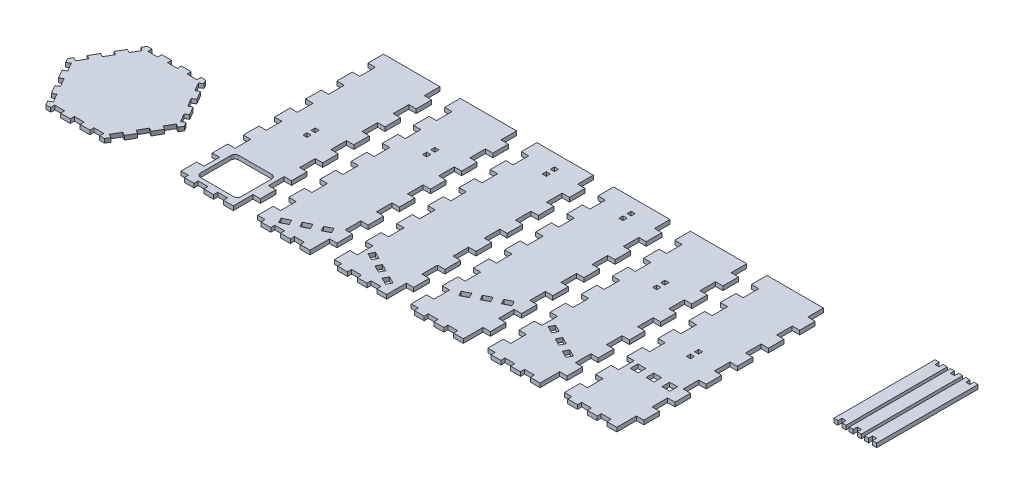
SolidWorks part; units mm, degrees
ref_plane "Front Plane" through (0, 0, 0) normal (0, 0, 1) x (1, 0, 0)
ref_plane "Top Plane" through (0, 0, 0) normal (0, 1, 0) x (1, 0, 0)
ref_plane "Right Plane" through (0, 0, 0) normal (1, 0, 0) x (0, 0, -1)
sketch "Sketch1" plane through (0, 0, 0) normal (0, 1, 0) x (1, 0, 0)
  line L0 (-22.87, -39.612) -> (-19.175, -39.612)
  line L13 (-19.175, -39.612) -> (-19.175, -36.412)
  line L14 (-19.175, -36.412) -> (-11.505, -36.412)
  line L15 (-11.505, -36.412) -> (-11.505, -39.612)
  line L16 (-11.505, -39.612) -> (-3.835, -39.612)
  line L17 (-3.835, -39.612) -> (-3.835, -36.412)
  line L18 (-3.835, -36.412) -> (3.835, -36.412)
  line L19 (3.835, -36.412) -> (3.835, -39.612)
  line L21 (-45.74, 0) -> (-43.8925, -3.2)
  line L22 (3.835, -39.612) -> (11.505, -39.612)
  line L23 (11.505, -39.612) -> (11.505, -36.412)
  line L24 (11.505, -36.412) -> (19.175, -36.412)
  line L25 (19.175, -36.412) -> (19.175, -39.612)
  line L26 (19.175, -39.612) -> (22.87, -39.612)
  line L27 (22.87, -39.612) -> (24.7175, -36.412)
  line L28 (45.74, 0) -> (22.87, 39.612) construction
  line L29 (24.7175, -36.412) -> (21.9462, -34.812)
  line L30 (21.9462, -34.812) -> (25.7812, -28.1696)
  line L31 (25.7812, -28.1696) -> (28.5525, -29.7696)
  line L32 (28.5525, -29.7696) -> (32.3875, -23.1272)
  line L33 (32.3875, -23.1272) -> (29.6162, -21.5272)
  line L34 (29.6162, -21.5272) -> (33.4512, -14.8848)
  line L35 (33.4512, -14.8848) -> (36.2225, -16.4848)
  line L36 (36.2225, -16.4848) -> (40.0575, -9.8424)
  line L37 (40.0575, -9.8424) -> (37.2862, -8.2424)
  line L38 (37.2862, -8.2424) -> (41.1212, -1.6)
  line L39 (41.1212, -1.6) -> (43.8925, -3.2)
  line L40 (43.8925, -3.2) -> (45.74, 0)
  line L41 (45.74, 0) -> (43.8925, 3.2)
  line L42 (22.87, 39.612) -> (-22.87, 39.612) construction
  line L43 (-22.87, 39.612) -> (-45.74, 0) construction
  line L44 (43.8925, 3.2) -> (41.1212, 1.6)
  line L45 (41.1212, 1.6) -> (37.2862, 8.2424)
  line L46 (37.2862, 8.2424) -> (40.0575, 9.8424)
  line L47 (40.0575, 9.8424) -> (36.2225, 16.4848)
  line L48 (36.2225, 16.4848) -> (33.4512, 14.8848)
  line L49 (33.4512, 14.8848) -> (29.6162, 21.5272)
  line L50 (29.6162, 21.5272) -> (32.3875, 23.1272)
  line L51 (32.3875, 23.1272) -> (28.5525, 29.7696)
  line L52 (28.5525, 29.7696) -> (25.7812, 28.1696)
  line L53 (25.7812, 28.1696) -> (21.9462, 34.812)
  line L54 (21.9462, 34.812) -> (24.7175, 36.412)
  line L55 (24.7175, 36.412) -> (22.87, 39.612)
  line L56 (22.87, 39.612) -> (19.175, 39.612)
  line L57 (-45.74, 0) -> (-22.87, -39.612) construction
  line L58 (-22.87, -39.612) -> (22.87, -39.612) construction
  line L59 (19.175, 39.612) -> (19.175, 36.412)
  line L60 (19.175, 36.412) -> (11.505, 36.412)
  line L61 (11.505, 36.412) -> (11.505, 39.612)
  line L62 (11.505, 39.612) -> (3.835, 39.612)
  line L63 (3.835, 39.612) -> (3.835, 36.412)
  line L64 (3.835, 36.412) -> (-3.835, 36.412)
  line L65 (-3.835, 36.412) -> (-3.835, 39.612)
  line L66 (-3.835, 39.612) -> (-11.505, 39.612)
  line L67 (-11.505, 39.612) -> (-11.505, 36.412)
  line L68 (-11.505, 36.412) -> (-19.175, 36.412)
  line L69 (-19.175, 36.412) -> (-19.175, 39.612)
  line L70 (-19.175, 39.612) -> (-22.87, 39.612)
  line L71 (-22.87, 39.612) -> (-24.7175, 36.412)
  line L72 (22.87, -39.612) -> (45.74, 0) construction
  line L73 (-43.8925, -3.2) -> (-41.1212, -1.6)
  line L74 (-24.7175, 36.412) -> (-21.9462, 34.812)
  line L75 (-21.9462, 34.812) -> (-25.7812, 28.1696)
  line L76 (-25.7812, 28.1696) -> (-28.5525, 29.7696)
  line L77 (-28.5525, 29.7696) -> (-32.3875, 23.1272)
  line L78 (-32.3875, 23.1272) -> (-29.6162, 21.5272)
  line L79 (-29.6162, 21.5272) -> (-33.4512, 14.8848)
  line L80 (-33.4512, 14.8848) -> (-36.2225, 16.4848)
  line L81 (-36.2225, 16.4848) -> (-40.0575, 9.8424)
  line L82 (-40.0575, 9.8424) -> (-37.2862, 8.2424)
  line L83 (-37.2862, 8.2424) -> (-41.1212, 1.6)
  line L84 (-41.1212, 1.6) -> (-43.8925, 3.2)
  line L85 (-43.8925, 3.2) -> (-45.74, 0)
  line L86 (-41.1212, -1.6) -> (-37.2862, -8.2424)
  line L87 (-37.2862, -8.2424) -> (-40.0575, -9.8424)
  line L88 (-40.0575, -9.8424) -> (-36.2225, -16.4848)
  line L89 (-36.2225, -16.4848) -> (-33.4512, -14.8848)
  line L90 (-33.4512, -14.8848) -> (-29.6162, -21.5272)
  line L91 (-29.6162, -21.5272) -> (-32.3875, -23.1272)
  line L92 (-32.3875, -23.1272) -> (-28.5525, -29.7696)
  line L93 (-28.5525, -29.7696) -> (-25.7812, -28.1696)
  line L94 (-25.7812, -28.1696) -> (-21.9462, -34.812)
  line L95 (-21.9462, -34.812) -> (-24.7175, -36.412)
  line L96 (-24.7175, -36.412) -> (-22.87, -39.612)
  line L97 (-21.9462, -34.812) -> (-19.175, -39.612) construction
  line L102 (19.175, -36.412) -> (24.7175, -36.412) construction
  line L103 (-19.175, -36.412) -> (-24.7175, -36.412) construction
  line L104 (80.5528, -34.8794) -> (88.2227, -34.8794)
  line L105 (88.2227, -34.8794) -> (88.2227, -31.6794)
  line L106 (88.2227, -31.6794) -> (95.8927, -31.6794)
  line L107 (95.8927, -31.6794) -> (95.8927, -34.8794)
  line L108 (95.8927, -34.8794) -> (103.5627, -34.8794)
  line L109 (103.5627, -34.8794) -> (103.5627, -31.6794)
  line L110 (103.5627, -31.6794) -> (111.2327, -31.6794)
  line L111 (111.2327, -31.6794) -> (111.2327, -34.8794)
  line L112 (111.2327, -34.8794) -> (118.9027, -34.8794)
  line L113 (80.5528, -34.8794) -> (80.5528, -31.6794)
  line L114 (80.5528, -31.6794) -> (74.8102, -31.6794)
  line L115 (74.8102, -31.6794) -> (74.8102, -19.4911)
  line L116 (74.8102, -19.4911) -> (80.5528, -19.4911)
  line L117 (80.5528, -19.4911) -> (80.5528, -7.3028)
  line L118 (80.5528, -7.3028) -> (74.8102, -7.3028)
  line L121 (118.9027, -7.3028) -> (124.6452, -7.3028)
  line L122 (124.6452, -7.3028) -> (124.6452, -19.4911)
  line L123 (124.6452, -19.4911) -> (118.9027, -19.4911)
  line L124 (118.9027, -19.4911) -> (118.9027, -34.8794)
  line L126 (21.9462, -34.812) -> (19.175, -39.612) construction
  line L250 (140.5528, -34.8794) -> (148.2227, -34.8794)
  line L265 (148.2227, -34.8794) -> (148.2227, -31.6794)
  line L266 (148.2227, -31.6794) -> (155.8927, -31.6794)
  line L267 (155.8927, -31.6794) -> (155.8927, -34.8794)
  line L268 (155.8927, -34.8794) -> (163.5627, -34.8794)
  line L269 (163.5627, -34.8794) -> (163.5627, -31.6794)
  line L270 (74.8102, -7.3028) -> (74.8102, 4.8855)
  line L271 (74.8102, 4.8855) -> (80.5528, 4.8855)
  line L272 (80.5528, 4.8855) -> (80.5528, 17.0739)
  line L273 (80.5528, 17.0739) -> (74.8102, 17.0739)
  line L274 (74.8102, 17.0739) -> (74.8102, 29.2622)
  line L275 (74.8102, 29.2622) -> (80.5528, 29.2622)
  line L276 (80.5528, 29.2622) -> (80.5528, 41.4505)
  line L277 (80.5528, 41.4505) -> (74.8102, 41.4505)
  line L278 (74.8102, 41.4505) -> (74.8102, 53.6388)
  line L279 (74.8102, 53.6388) -> (80.5528, 53.6388)
  line L280 (80.5528, 53.6388) -> (80.5528, 65.8271)
  line L281 (80.5528, 65.8271) -> (74.8102, 65.8271)
  line L282 (74.8102, 65.8271) -> (74.8102, 78.0154)
  line L283 (74.8102, 78.0154) -> (80.5528, 78.0154)
  line L284 (80.5528, 78.0154) -> (80.5528, 90.2037)
  line L285 (80.5528, 90.2037) -> (74.8102, 90.2037)
  line L286 (74.8102, 90.2037) -> (74.8102, 102.392)
  line L287 (74.8102, 102.392) -> (80.5528, 102.392)
  line L288 (80.5528, 102.392) -> (80.5528, 114.5803)
  line L289 (80.5528, 114.5803) -> (74.8102, 114.5803)
  line L290 (74.8102, 114.5803) -> (74.8102, 126.7686)
  line L291 (118.9027, -7.3028) -> (118.9027, 4.8855)
  line L292 (118.9027, 4.8855) -> (124.6452, 4.8855)
  line L293 (124.6452, 4.8855) -> (124.6452, 17.0739)
  line L294 (124.6452, 17.0739) -> (118.9027, 17.0739)
  line L295 (118.9027, 17.0739) -> (118.9027, 29.2622)
  line L296 (118.9027, 29.2622) -> (124.6452, 29.2622)
  line L297 (124.6452, 29.2622) -> (124.6452, 41.4505)
  line L298 (124.6452, 41.4505) -> (118.9027, 41.4505)
  line L299 (118.9027, 41.4505) -> (118.9027, 53.6388)
  line L300 (118.9027, 53.6388) -> (124.6452, 53.6388)
  line L301 (124.6452, 53.6388) -> (124.6452, 65.8271)
  line L302 (124.6452, 65.8271) -> (118.9027, 65.8271)
  line L303 (118.9027, 65.8271) -> (118.9027, 78.0154)
  line L304 (118.9027, 78.0154) -> (124.6452, 78.0154)
  line L305 (124.6452, 78.0154) -> (124.6452, 90.2037)
  line L306 (124.6452, 90.2037) -> (118.9027, 90.2037)
  line L307 (118.9027, 90.2037) -> (118.9027, 102.392)
  line L308 (118.9027, 102.392) -> (124.6452, 102.392)
  line L309 (124.6452, 102.392) -> (124.6452, 114.5803)
  line L310 (124.6452, 114.5803) -> (118.9027, 114.5803)
  line L311 (118.9027, 114.5803) -> (118.9027, 126.7686)
  line L312 (163.5627, -31.6794) -> (171.2327, -31.6794)
  line L313 (171.2327, -31.6794) -> (171.2327, -34.8794)
  line L314 (171.2327, -34.8794) -> (178.9027, -34.8794)
  line L315 (140.5528, -34.8794) -> (140.5528, -31.6794)
  line L316 (140.5528, -31.6794) -> (134.8102, -31.6794)
  line L317 (134.8102, -31.6794) -> (134.8102, -19.4911)
  line L318 (134.8102, -19.4911) -> (140.5528, -19.4911)
  line L319 (140.5528, -19.4911) -> (140.5528, -7.3028)
  line L320 (140.5528, -7.3028) -> (134.8102, -7.3028)
  line L322 (178.9027, -7.3028) -> (184.6452, -7.3028)
  line L323 (184.6452, -7.3028) -> (184.6452, -19.4911)
  line L324 (184.6452, -19.4911) -> (178.9027, -19.4911)
  line L325 (178.9027, -19.4911) -> (178.9027, -34.8794)
  line L326 (134.8102, -7.3028) -> (134.8102, 4.8855)
  line L327 (134.8102, 4.8855) -> (140.5528, 4.8855)
  line L328 (140.5528, 4.8855) -> (140.5528, 17.0739)
  line L329 (140.5528, 17.0739) -> (134.8102, 17.0739)
  line L330 (134.8102, 17.0739) -> (134.8102, 29.2622)
  line L331 (134.8102, 29.2622) -> (140.5528, 29.2622)
  line L332 (140.5528, 29.2622) -> (140.5528, 41.4505)
  line L333 (140.5528, 41.4505) -> (134.8102, 41.4505)
  line L334 (134.8102, 41.4505) -> (134.8102, 53.6388)
  line L335 (134.8102, 53.6388) -> (140.5528, 53.6388)
  line L336 (140.5528, 53.6388) -> (140.5528, 65.8271)
  line L337 (140.5528, 65.8271) -> (134.8102, 65.8271)
  line L338 (134.8102, 65.8271) -> (134.8102, 78.0154)
  line L339 (134.8102, 78.0154) -> (140.5528, 78.0154)
  line L340 (140.5528, 78.0154) -> (140.5528, 90.2037)
  line L341 (140.5528, 90.2037) -> (134.8102, 90.2037)
  line L342 (134.8102, 90.2037) -> (134.8102, 102.392)
  line L343 (134.8102, 102.392) -> (140.5528, 102.392)
  line L344 (140.5528, 102.392) -> (140.5528, 114.5803)
  line L345 (140.5528, 114.5803) -> (134.8102, 114.5803)
  line L346 (134.8102, 114.5803) -> (134.8102, 126.7686)
  line L347 (178.9027, -7.3028) -> (178.9027, 4.8855)
  line L348 (178.9027, 4.8855) -> (184.6452, 4.8855)
  line L349 (184.6452, 4.8855) -> (184.6452, 17.0739)
  line L350 (184.6452, 17.0739) -> (178.9027, 17.0739)
  line L351 (178.9027, 17.0739) -> (178.9027, 29.2622)
  line L352 (178.9027, 29.2622) -> (184.6452, 29.2622)
  line L353 (184.6452, 29.2622) -> (184.6452, 41.4505)
  line L354 (184.6452, 41.4505) -> (178.9027, 41.4505)
  line L355 (178.9027, 41.4505) -> (178.9027, 53.6388)
  line L356 (178.9027, 53.6388) -> (184.6452, 53.6388)
  line L357 (184.6452, 53.6388) -> (184.6452, 65.8271)
  line L358 (184.6452, 65.8271) -> (178.9027, 65.8271)
  line L359 (178.9027, 65.8271) -> (178.9027, 78.0154)
  line L360 (178.9027, 78.0154) -> (184.6452, 78.0154)
  line L361 (184.6452, 78.0154) -> (184.6452, 90.2037)
  line L362 (184.6452, 90.2037) -> (178.9027, 90.2037)
  line L363 (178.9027, 90.2037) -> (178.9027, 102.392)
  line L364 (178.9027, 102.392) -> (184.6452, 102.392)
  line L365 (184.6452, 102.392) -> (184.6452, 114.5803)
  line L366 (184.6452, 114.5803) -> (178.9027, 114.5803)
  line L367 (178.9027, 114.5803) -> (178.9027, 126.7686)
  line L369 (200.5528, -34.8794) -> (208.2227, -34.8794)
  line L370 (208.2227, -34.8794) -> (208.2227, -31.6794)
  line L371 (208.2227, -31.6794) -> (215.8927, -31.6794)
  line L372 (215.8927, -31.6794) -> (215.8927, -34.8794)
  line L373 (215.8927, -34.8794) -> (223.5627, -34.8794)
  line L374 (223.5627, -34.8794) -> (223.5627, -31.6794)
  line L375 (223.5627, -31.6794) -> (231.2327, -31.6794)
  line L376 (231.2327, -31.6794) -> (231.2327, -34.8794)
  line L377 (231.2327, -34.8794) -> (238.9027, -34.8794)
  line L378 (200.5528, -34.8794) -> (200.5528, -31.6794)
  line L379 (200.5528, -31.6794) -> (194.8102, -31.6794)
  line L380 (194.8102, -31.6794) -> (194.8102, -19.4911)
  line L381 (194.8102, -19.4911) -> (200.5528, -19.4911)
  line L382 (200.5528, -19.4911) -> (200.5528, -7.3028)
  line L383 (200.5528, -7.3028) -> (194.8102, -7.3028)
  line L385 (238.9027, -7.3028) -> (244.6452, -7.3028)
  line L386 (244.6452, -7.3028) -> (244.6452, -19.4911)
  line L387 (244.6452, -19.4911) -> (238.9027, -19.4911)
  line L388 (238.9027, -19.4911) -> (238.9027, -34.8794)
  line L389 (194.8102, -7.3028) -> (194.8102, 4.8855)
  line L390 (194.8102, 4.8855) -> (200.5528, 4.8855)
  line L391 (200.5528, 4.8855) -> (200.5528, 17.0739)
  line L392 (200.5528, 17.0739) -> (194.8102, 17.0739)
  line L393 (194.8102, 17.0739) -> (194.8102, 29.2622)
  line L394 (194.8102, 29.2622) -> (200.5528, 29.2622)
  line L395 (200.5528, 29.2622) -> (200.5528, 41.4505)
  line L396 (200.5528, 41.4505) -> (194.8102, 41.4505)
  line L397 (194.8102, 41.4505) -> (194.8102, 53.6388)
  line L398 (194.8102, 53.6388) -> (200.5528, 53.6388)
  line L399 (200.5528, 53.6388) -> (200.5528, 65.8271)
  line L400 (200.5528, 65.8271) -> (194.8102, 65.8271)
  line L401 (194.8102, 65.8271) -> (194.8102, 78.0154)
  line L402 (194.8102, 78.0154) -> (200.5528, 78.0154)
  line L403 (200.5528, 78.0154) -> (200.5528, 90.2037)
  line L404 (200.5528, 90.2037) -> (194.8102, 90.2037)
  line L405 (194.8102, 90.2037) -> (194.8102, 102.392)
  line L406 (194.8102, 102.392) -> (200.5528, 102.392)
  line L407 (200.5528, 102.392) -> (200.5528, 114.5803)
  line L408 (200.5528, 114.5803) -> (194.8102, 114.5803)
  line L409 (194.8102, 114.5803) -> (194.8102, 126.7686)
  line L410 (238.9027, -7.3028) -> (238.9027, 4.8855)
  line L411 (238.9027, 4.8855) -> (244.6452, 4.8855)
  line L412 (244.6452, 4.8855) -> (244.6452, 17.0739)
  line L413 (244.6452, 17.0739) -> (238.9027, 17.0739)
  line L414 (238.9027, 17.0739) -> (238.9027, 29.2622)
  line L415 (238.9027, 29.2622) -> (244.6452, 29.2622)
  line L416 (244.6452, 29.2622) -> (244.6452, 41.4505)
  line L417 (244.6452, 41.4505) -> (238.9027, 41.4505)
  line L418 (238.9027, 41.4505) -> (238.9027, 53.6388)
  line L419 (238.9027, 53.6388) -> (244.6452, 53.6388)
  line L420 (244.6452, 53.6388) -> (244.6452, 65.8271)
  line L421 (244.6452, 65.8271) -> (238.9027, 65.8271)
  line L422 (238.9027, 65.8271) -> (238.9027, 78.0154)
  line L423 (238.9027, 78.0154) -> (244.6452, 78.0154)
  line L424 (244.6452, 78.0154) -> (244.6452, 90.2037)
  line L425 (244.6452, 90.2037) -> (238.9027, 90.2037)
  line L426 (238.9027, 90.2037) -> (238.9027, 102.392)
  line L427 (238.9027, 102.392) -> (244.6452, 102.392)
  line L428 (244.6452, 102.392) -> (244.6452, 114.5803)
  line L429 (244.6452, 114.5803) -> (238.9027, 114.5803)
  line L430 (238.9027, 114.5803) -> (238.9027, 126.7686)
  line L432 (260.5528, -34.8794) -> (268.2227, -34.8794)
  line L433 (268.2227, -34.8794) -> (268.2227, -31.6794)
  line L434 (268.2227, -31.6794) -> (275.8927, -31.6794)
  line L435 (275.8927, -31.6794) -> (275.8927, -34.8794)
  line L436 (275.8927, -34.8794) -> (283.5627, -34.8794)
  line L437 (283.5627, -34.8794) -> (283.5627, -31.6794)
  line L438 (283.5627, -31.6794) -> (291.2327, -31.6794)
  line L439 (291.2327, -31.6794) -> (291.2327, -34.8794)
  line L440 (291.2327, -34.8794) -> (298.9027, -34.8794)
  line L441 (260.5528, -34.8794) -> (260.5528, -31.6794)
  line L442 (260.5528, -31.6794) -> (254.8102, -31.6794)
  line L443 (254.8102, -31.6794) -> (254.8102, -19.4911)
  line L444 (254.8102, -19.4911) -> (260.5528, -19.4911)
  line L445 (260.5528, -19.4911) -> (260.5528, -7.3028)
  line L446 (260.5528, -7.3028) -> (254.8102, -7.3028)
  line L448 (298.9027, -7.3028) -> (304.6452, -7.3028)
  line L449 (304.6452, -7.3028) -> (304.6452, -19.4911)
  line L450 (304.6452, -19.4911) -> (298.9027, -19.4911)
  line L451 (298.9027, -19.4911) -> (298.9027, -34.8794)
  line L452 (254.8102, -7.3028) -> (254.8102, 4.8855)
  line L453 (254.8102, 4.8855) -> (260.5528, 4.8855)
  line L454 (260.5528, 4.8855) -> (260.5528, 17.0739)
  line L455 (260.5528, 17.0739) -> (254.8102, 17.0739)
  line L456 (254.8102, 17.0739) -> (254.8102, 29.2622)
  line L457 (254.8102, 29.2622) -> (260.5528, 29.2622)
  line L458 (260.5528, 29.2622) -> (260.5528, 41.4505)
  line L459 (260.5528, 41.4505) -> (254.8102, 41.4505)
  line L460 (254.8102, 41.4505) -> (254.8102, 53.6388)
  line L461 (254.8102, 53.6388) -> (260.5528, 53.6388)
  line L462 (260.5528, 53.6388) -> (260.5528, 65.8271)
  line L463 (260.5528, 65.8271) -> (254.8102, 65.8271)
  line L464 (254.8102, 65.8271) -> (254.8102, 78.0154)
  line L465 (254.8102, 78.0154) -> (260.5528, 78.0154)
  line L466 (260.5528, 78.0154) -> (260.5528, 90.2037)
  line L467 (260.5528, 90.2037) -> (254.8102, 90.2037)
  line L468 (254.8102, 90.2037) -> (254.8102, 102.392)
  line L469 (254.8102, 102.392) -> (260.5528, 102.392)
  line L470 (260.5528, 102.392) -> (260.5528, 114.5803)
  line L471 (260.5528, 114.5803) -> (254.8102, 114.5803)
  line L472 (254.8102, 114.5803) -> (254.8102, 126.7686)
  line L473 (298.9027, -7.3028) -> (298.9027, 4.8855)
  line L474 (298.9027, 4.8855) -> (304.6452, 4.8855)
  line L475 (304.6452, 4.8855) -> (304.6452, 17.0739)
  line L476 (304.6452, 17.0739) -> (298.9027, 17.0739)
  line L477 (298.9027, 17.0739) -> (298.9027, 29.2622)
  line L478 (298.9027, 29.2622) -> (304.6452, 29.2622)
  line L479 (304.6452, 29.2622) -> (304.6452, 41.4505)
  line L480 (304.6452, 41.4505) -> (298.9027, 41.4505)
  line L481 (298.9027, 41.4505) -> (298.9027, 53.6388)
  line L482 (298.9027, 53.6388) -> (304.6452, 53.6388)
  line L483 (304.6452, 53.6388) -> (304.6452, 65.8271)
  line L484 (304.6452, 65.8271) -> (298.9027, 65.8271)
  line L485 (298.9027, 65.8271) -> (298.9027, 78.0154)
  line L486 (298.9027, 78.0154) -> (304.6452, 78.0154)
  line L487 (304.6452, 78.0154) -> (304.6452, 90.2037)
  line L488 (304.6452, 90.2037) -> (298.9027, 90.2037)
  line L489 (298.9027, 90.2037) -> (298.9027, 102.392)
  line L490 (298.9027, 102.392) -> (304.6452, 102.392)
  line L491 (304.6452, 102.392) -> (304.6452, 114.5803)
  line L492 (304.6452, 114.5803) -> (298.9027, 114.5803)
  line L493 (298.9027, 114.5803) -> (298.9027, 126.7686)
  line L495 (320.5528, -34.8794) -> (328.2227, -34.8794)
  line L496 (328.2227, -34.8794) -> (328.2227, -31.6794)
  line L497 (328.2227, -31.6794) -> (335.8927, -31.6794)
  line L498 (335.8927, -31.6794) -> (335.8927, -34.8794)
  line L499 (335.8927, -34.8794) -> (343.5627, -34.8794)
  line L500 (343.5627, -34.8794) -> (343.5627, -31.6794)
  line L501 (343.5627, -31.6794) -> (351.2327, -31.6794)
  line L502 (351.2327, -31.6794) -> (351.2327, -34.8794)
  line L503 (351.2327, -34.8794) -> (358.9027, -34.8794)
  line L504 (320.5528, -34.8794) -> (320.5528, -31.6794)
  line L505 (320.5528, -31.6794) -> (314.8102, -31.6794)
  line L506 (314.8102, -31.6794) -> (314.8102, -19.4911)
  line L507 (314.8102, -19.4911) -> (320.5528, -19.4911)
  line L508 (320.5528, -19.4911) -> (320.5528, -7.3028)
  line L509 (320.5528, -7.3028) -> (314.8102, -7.3028)
  line L511 (358.9027, -7.3028) -> (364.6452, -7.3028)
  line L512 (364.6452, -7.3028) -> (364.6452, -19.4911)
  line L513 (364.6452, -19.4911) -> (358.9027, -19.4911)
  line L514 (358.9027, -19.4911) -> (358.9027, -34.8794)
  line L515 (314.8102, -7.3028) -> (314.8102, 4.8855)
  line L516 (314.8102, 4.8855) -> (320.5528, 4.8855)
  line L517 (320.5528, 4.8855) -> (320.5528, 17.0739)
  line L518 (320.5528, 17.0739) -> (314.8102, 17.0739)
  line L519 (314.8102, 17.0739) -> (314.8102, 29.2622)
  line L520 (314.8102, 29.2622) -> (320.5528, 29.2622)
  line L521 (320.5528, 29.2622) -> (320.5528, 41.4505)
  line L522 (320.5528, 41.4505) -> (314.8102, 41.4505)
  line L523 (314.8102, 41.4505) -> (314.8102, 53.6388)
  line L524 (314.8102, 53.6388) -> (320.5528, 53.6388)
  line L525 (320.5528, 53.6388) -> (320.5528, 65.8271)
  line L526 (320.5528, 65.8271) -> (314.8102, 65.8271)
  line L527 (314.8102, 65.8271) -> (314.8102, 78.0154)
  line L528 (314.8102, 78.0154) -> (320.5528, 78.0154)
  line L529 (320.5528, 78.0154) -> (320.5528, 90.2037)
  line L530 (320.5528, 90.2037) -> (314.8102, 90.2037)
  line L531 (314.8102, 90.2037) -> (314.8102, 102.392)
  line L532 (314.8102, 102.392) -> (320.5528, 102.392)
  line L533 (320.5528, 102.392) -> (320.5528, 114.5803)
  line L534 (320.5528, 114.5803) -> (314.8102, 114.5803)
  line L535 (314.8102, 114.5803) -> (314.8102, 126.7686)
  line L536 (358.9027, -7.3028) -> (358.9027, 4.8855)
  line L537 (358.9027, 4.8855) -> (364.6452, 4.8855)
  line L538 (364.6452, 4.8855) -> (364.6452, 17.0739)
  line L539 (364.6452, 17.0739) -> (358.9027, 17.0739)
  line L540 (358.9027, 17.0739) -> (358.9027, 29.2622)
  line L541 (358.9027, 29.2622) -> (364.6452, 29.2622)
  line L542 (364.6452, 29.2622) -> (364.6452, 41.4505)
  line L543 (364.6452, 41.4505) -> (358.9027, 41.4505)
  line L544 (358.9027, 41.4505) -> (358.9027, 53.6388)
  line L545 (358.9027, 53.6388) -> (364.6452, 53.6388)
  line L546 (364.6452, 53.6388) -> (364.6452, 65.8271)
  line L547 (364.6452, 65.8271) -> (358.9027, 65.8271)
  line L548 (358.9027, 65.8271) -> (358.9027, 78.0154)
  line L549 (358.9027, 78.0154) -> (364.6452, 78.0154)
  line L550 (364.6452, 78.0154) -> (364.6452, 90.2037)
  line L551 (364.6452, 90.2037) -> (358.9027, 90.2037)
  line L552 (358.9027, 90.2037) -> (358.9027, 102.392)
  line L553 (358.9027, 102.392) -> (364.6452, 102.392)
  line L554 (364.6452, 102.392) -> (364.6452, 114.5803)
  line L555 (364.6452, 114.5803) -> (358.9027, 114.5803)
  line L556 (358.9027, 114.5803) -> (358.9027, 126.7686)
  line L558 (380.5528, -34.8794) -> (388.2227, -34.8794)
  line L559 (388.2227, -34.8794) -> (388.2227, -31.6794)
  line L560 (388.2227, -31.6794) -> (395.8927, -31.6794)
  line L561 (395.8927, -31.6794) -> (395.8927, -34.8794)
  line L562 (395.8927, -34.8794) -> (403.5627, -34.8794)
  line L563 (403.5627, -34.8794) -> (403.5627, -31.6794)
  line L564 (403.5627, -31.6794) -> (411.2327, -31.6794)
  line L565 (411.2327, -31.6794) -> (411.2327, -34.8794)
  line L566 (411.2327, -34.8794) -> (418.9027, -34.8794)
  line L567 (380.5528, -34.8794) -> (380.5528, -31.6794)
  line L568 (380.5528, -31.6794) -> (374.8102, -31.6794)
  line L569 (374.8102, -31.6794) -> (374.8102, -19.4911)
  line L570 (374.8102, -19.4911) -> (380.5528, -19.4911)
  line L571 (380.5528, -19.4911) -> (380.5528, -7.3028)
  line L572 (380.5528, -7.3028) -> (374.8102, -7.3028)
  line L574 (418.9027, -7.3028) -> (424.6452, -7.3028)
  line L575 (424.6452, -7.3028) -> (424.6452, -19.4911)
  line L576 (424.6452, -19.4911) -> (418.9027, -19.4911)
  line L577 (418.9027, -19.4911) -> (418.9027, -34.8794)
  line L578 (374.8102, -7.3028) -> (374.8102, 4.8855)
  line L579 (374.8102, 4.8855) -> (380.5528, 4.8855)
  line L580 (380.5528, 4.8855) -> (380.5528, 17.0739)
  line L581 (380.5528, 17.0739) -> (374.8102, 17.0739)
  line L582 (374.8102, 17.0739) -> (374.8102, 29.2622)
  line L583 (374.8102, 29.2622) -> (380.5528, 29.2622)
  line L584 (380.5528, 29.2622) -> (380.5528, 41.4505)
  line L585 (380.5528, 41.4505) -> (374.8102, 41.4505)
  line L586 (374.8102, 41.4505) -> (374.8102, 53.6388)
  line L587 (374.8102, 53.6388) -> (380.5528, 53.6388)
  line L588 (380.5528, 53.6388) -> (380.5528, 65.8271)
  line L589 (380.5528, 65.8271) -> (374.8102, 65.8271)
  line L590 (374.8102, 65.8271) -> (374.8102, 78.0154)
  line L591 (374.8102, 78.0154) -> (380.5528, 78.0154)
  line L592 (380.5528, 78.0154) -> (380.5528, 90.2037)
  line L593 (380.5528, 90.2037) -> (374.8102, 90.2037)
  line L594 (374.8102, 90.2037) -> (374.8102, 102.392)
  line L595 (374.8102, 102.392) -> (380.5528, 102.392)
  line L596 (380.5528, 102.392) -> (380.5528, 114.5803)
  line L597 (380.5528, 114.5803) -> (374.8102, 114.5803)
  line L598 (374.8102, 114.5803) -> (374.8102, 126.7686)
  line L599 (418.9027, -7.3028) -> (418.9027, 4.8855)
  line L600 (418.9027, 4.8855) -> (424.6452, 4.8855)
  line L601 (424.6452, 4.8855) -> (424.6452, 17.0739)
  line L602 (424.6452, 17.0739) -> (418.9027, 17.0739)
  line L603 (418.9027, 17.0739) -> (418.9027, 29.2622)
  line L604 (418.9027, 29.2622) -> (424.6452, 29.2622)
  line L605 (424.6452, 29.2622) -> (424.6452, 41.4505)
  line L606 (424.6452, 41.4505) -> (418.9027, 41.4505)
  line L607 (418.9027, 41.4505) -> (418.9027, 53.6388)
  line L608 (418.9027, 53.6388) -> (424.6452, 53.6388)
  line L609 (424.6452, 53.6388) -> (424.6452, 65.8271)
  line L610 (424.6452, 65.8271) -> (418.9027, 65.8271)
  line L611 (418.9027, 65.8271) -> (418.9027, 78.0154)
  line L612 (418.9027, 78.0154) -> (424.6452, 78.0154)
  line L613 (424.6452, 78.0154) -> (424.6452, 90.2037)
  line L614 (424.6452, 90.2037) -> (418.9027, 90.2037)
  line L615 (418.9027, 90.2037) -> (418.9027, 102.392)
  line L616 (418.9027, 102.392) -> (424.6452, 102.392)
  line L617 (424.6452, 102.392) -> (424.6452, 114.5803)
  line L618 (424.6452, 114.5803) -> (418.9027, 114.5803)
  line L619 (418.9027, 114.5803) -> (418.9027, 126.7686)
  line L621 (145.8635, -24.5223) -> (151.4092, -21.7501)
  line L622 (145.8635, -24.5223) -> (147.8308, -28.458)
  line L623 (147.8308, -28.458) -> (153.3765, -25.6858)
  line L624 (151.4092, -21.7501) -> (153.3765, -25.6858)
  line L625 (156.9549, -18.9779) -> (162.5006, -16.2057)
  line L626 (156.9549, -18.9779) -> (158.9222, -22.9135)
  line L627 (158.9222, -22.9135) -> (164.4679, -20.1413)
  line L628 (162.5006, -16.2057) -> (164.4679, -20.1413)
  line L632 (168.0463, -13.4335) -> (173.592, -10.6612)
  line L633 (168.0463, -13.4335) -> (170.0136, -17.3691)
  line L634 (170.0136, -17.3691) -> (175.5593, -14.5969)
  line L635 (173.592, -10.6612) -> (175.5593, -14.5969)
  line L636 (118.9027, 126.7686) -> (74.8102, 126.7686)
  line L637 (134.8102, 126.7686) -> (178.9027, 126.7686)
  line L638 (194.8102, 126.7686) -> (238.9027, 126.7686)
  line L639 (254.8102, 126.7686) -> (298.9027, 126.7686)
  line L640 (314.8102, 126.7686) -> (358.9027, 126.7686)
  line L641 (374.8102, 126.7686) -> (418.9027, 126.7686)
  line L642 (-41.1212, -1.6) -> (-42.045, 0) construction
  line L643 (-42.045, 0) -> (-41.1212, 1.6) construction
  line L644 (41.1212, -1.6) -> (42.045, 0) construction
  line L645 (42.045, 0) -> (41.1212, 1.6) construction
  line L646 (-21.0225, -36.412) -> (-22.87, -39.612) construction
  line L647 (21.0225, -36.412) -> (22.87, -39.612) construction
  line L648 (138.7077, -28.0994) -> (145.8635, -24.5223) construction
  line L649 (173.592, -10.6612) -> (180.7477, -7.0842) construction
  line L650 (189.7277, 136.633) -> (189.7277, -43.0289) construction
  line L651 (138.7077, -34.8794) -> (180.7477, -34.8794) construction
  line L652 (205.8635, -10.6612) -> (203.8961, -14.5969)
  line L653 (209.4418, -17.3691) -> (203.8961, -14.5969)
  line L654 (211.4092, -13.4335) -> (209.4418, -17.3691)
  line L655 (211.4092, -13.4335) -> (205.8635, -10.6612)
  line L656 (216.9549, -16.2057) -> (214.9875, -20.1413)
  line L657 (220.5332, -22.9135) -> (214.9875, -20.1413)
  line L658 (222.5006, -18.9779) -> (220.5332, -22.9135)
  line L659 (222.5006, -18.9779) -> (216.9549, -16.2057)
  line L660 (228.0463, -21.7501) -> (226.0789, -25.6858)
  line L661 (231.6246, -28.458) -> (226.0789, -25.6858)
  line L662 (233.592, -24.5223) -> (231.6246, -28.458)
  line L663 (233.592, -24.5223) -> (228.0463, -21.7501)
  line L664 (252.6938, -7.0794) -> (309.7277, -7.0794) construction
  line L665 (258.7077, -34.8794) -> (300.7477, -34.8794) construction
  line L666 (258.7077, -11.9985) -> (267.8308, -7.438) construction
  line L667 (267.8308, -7.438) -> (265.8635, -3.5023)
  line L668 (265.8635, -3.5023) -> (271.4092, -0.7301)
  line L669 (271.4092, -0.7301) -> (273.3765, -4.6658)
  line L670 (273.3765, -4.6658) -> (267.8308, -7.438)
  line L671 (276.9549, 2.0421) -> (278.9222, -1.8935)
  line L672 (278.9222, -1.8935) -> (284.4679, 0.8787)
  line L673 (284.4679, 0.8787) -> (282.5006, 4.8143)
  line L674 (282.5006, 4.8143) -> (276.9549, 2.0421)
  line L675 (288.0463, 7.5865) -> (290.0136, 3.6509)
  line L676 (290.0136, 3.6509) -> (295.5593, 6.4231)
  line L677 (295.5593, 6.4231) -> (293.592, 10.3588)
  line L678 (293.592, 10.3588) -> (288.0463, 7.5865)
  line L679 (295.5593, 6.4231) -> (300.7477, 9.0167) construction
  line L680 (309.7277, 136.633) -> (309.7277, -43.0289) construction
  line L681 (325.8635, 10.3588) -> (331.4092, 7.5865)
  line L682 (323.8961, 6.4231) -> (325.8635, 10.3588)
  line L683 (329.4418, 3.6509) -> (323.8961, 6.4231)
  line L684 (331.4092, 7.5865) -> (329.4418, 3.6509)
  line L685 (336.9549, 4.8143) -> (342.5006, 2.0421)
  line L686 (334.9875, 0.8787) -> (336.9549, 4.8143)
  line L687 (340.5332, -1.8935) -> (334.9875, 0.8787)
  line L688 (342.5006, 2.0421) -> (340.5332, -1.8935)
  line L689 (346.0789, -4.6658) -> (351.6246, -7.438)
  line L690 (348.0463, -0.7301) -> (346.0789, -4.6658)
  line L691 (353.592, -3.5023) -> (348.0463, -0.7301)
  line L692 (351.6246, -7.438) -> (353.592, -3.5023)
  line L693 (384.2277, 16.3606) -> (384.2277, 10.3606)
  line L694 (384.2277, 10.3606) -> (390.4277, 10.3606)
  line L695 (390.4277, 10.3606) -> (390.4277, 16.3606)
  line L696 (390.4277, 16.3606) -> (384.2277, 16.3606)
  line L697 (396.6277, 16.3606) -> (396.6277, 10.3606)
  line L698 (396.6277, 10.3606) -> (402.8277, 10.3606)
  line L699 (402.8277, 10.3606) -> (402.8277, 16.3606)
  line L700 (402.8277, 16.3606) -> (396.6277, 16.3606)
  line L701 (409.0277, 16.3606) -> (409.0277, 10.3606)
  line L702 (409.0277, 10.3606) -> (415.2277, 10.3606)
  line L703 (415.2277, 10.3606) -> (415.2277, 16.3606)
  line L704 (415.2277, 16.3606) -> (409.0277, 16.3606)
  line L705 (384.2277, 10.3606) -> (380.5528, 10.3606) construction
  line L706 (415.2277, 10.3606) -> (418.9027, 10.3606) construction
  line L707 (86.7528, 1.5206) -> (112.7027, 1.5206)
  line L708 (112.7027, -28.4794) -> (86.7528, -28.4794)
  line L709 (83.7528, -1.4794) -> (83.7528, -25.4794)
  line L710 (115.7027, -1.4794) -> (115.7027, -25.4794)
  line L711 (249.7277, 136.633) -> (249.7277, -43.0289) construction
  line L712 (398.1277, 49.9606) -> (401.3277, 49.9606)
  line L713 (398.1277, 49.9606) -> (398.1277, 46.7606)
  line L714 (398.1277, 46.7606) -> (401.3277, 46.7606)
  line L715 (401.3277, 49.9606) -> (401.3277, 46.7606)
  line L716 (398.1277, 43.5606) -> (401.3277, 43.5606)
  line L717 (398.1277, 43.5606) -> (398.1277, 40.3606)
  line L718 (398.1277, 40.3606) -> (401.3277, 40.3606)
  line L719 (401.3277, 43.5606) -> (401.3277, 40.3606)
  line L720 (98.1277, 43.5606) -> (98.1277, 40.3606)
  line L721 (101.3277, 40.3606) -> (98.1277, 40.3606)
  line L722 (101.3277, 43.5606) -> (101.3277, 40.3606)
  line L723 (101.3277, 43.5606) -> (98.1277, 43.5606)
  line L724 (98.1277, 49.9606) -> (98.1277, 46.7606)
  line L725 (101.3277, 46.7606) -> (98.1277, 46.7606)
  line L726 (101.3277, 49.9606) -> (101.3277, 46.7606)
  line L727 (101.3277, 49.9606) -> (98.1277, 49.9606)
  line L728 (158.1277, 77.1606) -> (158.1277, 73.9606)
  line L729 (161.3277, 73.9606) -> (158.1277, 73.9606)
  line L730 (161.3277, 77.1606) -> (161.3277, 73.9606)
  line L731 (161.3277, 77.1606) -> (158.1277, 77.1606)
  line L732 (158.1277, 83.5606) -> (158.1277, 80.3606)
  line L733 (161.3277, 80.3606) -> (158.1277, 80.3606)
  line L734 (161.3277, 83.5606) -> (161.3277, 80.3606)
  line L735 (161.3277, 83.5606) -> (158.1277, 83.5606)
  line L736 (338.1277, 83.5606) -> (341.3277, 83.5606)
  line L737 (338.1277, 83.5606) -> (338.1277, 80.3606)
  line L738 (338.1277, 80.3606) -> (341.3277, 80.3606)
  line L739 (341.3277, 83.5606) -> (341.3277, 80.3606)
  line L740 (338.1277, 77.1606) -> (341.3277, 77.1606)
  line L741 (338.1277, 77.1606) -> (338.1277, 73.9606)
  line L742 (338.1277, 73.9606) -> (341.3277, 73.9606)
  line L743 (341.3277, 77.1606) -> (341.3277, 73.9606)
  line L744 (218.1277, 110.7606) -> (218.1277, 107.5606)
  line L745 (221.3277, 107.5606) -> (218.1277, 107.5606)
  line L746 (221.3277, 110.7606) -> (221.3277, 107.5606)
  line L747 (221.3277, 110.7606) -> (218.1277, 110.7606)
  line L748 (218.1277, 117.1606) -> (218.1277, 113.9606)
  line L749 (221.3277, 113.9606) -> (218.1277, 113.9606)
  line L750 (221.3277, 117.1606) -> (221.3277, 113.9606)
  line L751 (221.3277, 117.1606) -> (218.1277, 117.1606)
  line L752 (278.1277, 117.1606) -> (281.3277, 117.1606)
  line L753 (278.1277, 117.1606) -> (278.1277, 113.9606)
  line L754 (278.1277, 113.9606) -> (281.3277, 113.9606)
  line L755 (281.3277, 117.1606) -> (281.3277, 113.9606)
  line L756 (278.1277, 110.7606) -> (281.3277, 110.7606)
  line L757 (278.1277, 110.7606) -> (278.1277, 107.5606)
  line L758 (278.1277, 107.5606) -> (281.3277, 107.5606)
  line L759 (281.3277, 110.7606) -> (281.3277, 107.5606)
  line L760 (497.6107, 135.4038) -> (497.6107, 56.1838)
  line L761 (500.8107, 56.1838) -> (500.8107, 59.3838)
  line L762 (500.8107, 59.3838) -> (504.0107, 59.3838)
  line L763 (504.0107, 59.3838) -> (504.0107, 56.1838)
  line L764 (504.0107, 56.1838) -> (507.2107, 56.1838)
  line L765 (507.2107, 56.1838) -> (507.2107, 135.4038)
  line L766 (507.2107, 135.4038) -> (504.0107, 135.4038)
  line L767 (504.0107, 135.4038) -> (504.0107, 132.2038)
  line L768 (504.0107, 132.2038) -> (500.8107, 132.2038)
  line L769 (500.8107, 132.2038) -> (500.8107, 135.4038)
  line L770 (500.8107, 135.4038) -> (497.6107, 135.4038)
  line L771 (500.8107, 56.1838) -> (497.6107, 56.1838)
  line L772 (509.6107, 135.4038) -> (509.6107, 56.1838)
  line L773 (512.8107, 56.1838) -> (512.8107, 59.3838)
  line L774 (512.8107, 59.3838) -> (516.0107, 59.3838)
  line L775 (516.0107, 59.3838) -> (516.0107, 56.1838)
  line L776 (516.0107, 56.1838) -> (519.2107, 56.1838)
  line L777 (519.2107, 56.1838) -> (519.2107, 135.4038)
  line L778 (519.2107, 135.4038) -> (516.0107, 135.4038)
  line L779 (516.0107, 135.4038) -> (516.0107, 132.2038)
  line L780 (516.0107, 132.2038) -> (512.8107, 132.2038)
  line L781 (512.8107, 132.2038) -> (512.8107, 135.4038)
  line L782 (512.8107, 135.4038) -> (509.6107, 135.4038)
  line L783 (512.8107, 56.1838) -> (509.6107, 56.1838)
  line L784 (521.6107, 135.4038) -> (521.6107, 56.1838)
  line L785 (524.8107, 56.1838) -> (524.8107, 59.3838)
  line L786 (524.8107, 59.3838) -> (528.0107, 59.3838)
  line L787 (528.0107, 59.3838) -> (528.0107, 56.1838)
  line L788 (528.0107, 56.1838) -> (531.2107, 56.1838)
  line L789 (531.2107, 56.1838) -> (531.2107, 135.4038)
  line L790 (531.2107, 135.4038) -> (528.0107, 135.4038)
  line L791 (528.0107, 135.4038) -> (528.0107, 132.2038)
  line L792 (528.0107, 132.2038) -> (524.8107, 132.2038)
  line L793 (524.8107, 132.2038) -> (524.8107, 135.4038)
  line L794 (524.8107, 135.4038) -> (521.6107, 135.4038)
  line L795 (524.8107, 56.1838) -> (521.6107, 56.1838)
  line L796 (265.8635, -3.5023) -> (258.7077, -7.0794) construction
  line L797 (293.592, 10.3588) -> (300.7477, 13.9358) construction
  circle A0 centre (0, 0) radius 39.612 construction
  arc A5 (86.7528, -28.4794) -> (83.7528, -25.4794) centre (86.7528, -25.4794) cw
  arc A6 (83.7528, -1.4794) -> (86.7528, 1.5206) centre (86.7528, -1.4794) cw
  arc A7 (112.7027, 1.5206) -> (115.7027, -1.4794) centre (112.7027, -1.4794) cw
  arc A8 (115.7027, -25.4794) -> (112.7027, -28.4794) centre (112.7027, -25.4794) cw
  point P498 (304.6452, -13.3969)
  point P582 (158.1277, 81.9606)
  point P619 (0, 0)
  point P646 (0, 0)
  point P647 (0, 0)
  dimension "D9" = 79.224
  dimension "D66" = 38.3499
  dimension "D79" = 3.2
  dimension "D10" = 38.3499
  dimension "D83" = 5.7426
  dimension "D45" = 5.7426
  dimension "D12" = 120
  dimension "D2" = 3.695
  dimension "D3" = 7.67
  dimension "D5" = 38.3499
  dimension "D11" = 12.1883
  dimension "D13" = 3.2
  dimension "D14" = 5.5426
  dimension "D86" = 15.3883
  dimension "D17" = 6.2
  dimension "D18" = 6.2
  dimension "D22" = 158.448
  dimension "D23" = 72.824
  dimension "D24" = 84.0899
  dimension "D25" = 42.045
  dimension "D19" = 6.2
  dimension "D20" = 10.165
  dimension "D26" = 5.0825
  dimension "D21" = 42.04
  dimension "D27" = 38.3499
  dimension "D28" = 1.845
  dimension "D33" = 42.04
  dimension "D34" = 1.845
  dimension "D35" = 38.3499
  dimension "D37" = 6.2
  dimension "D38" = 6.2
  dimension "D39" = 6.2
  dimension "D41" = 26.56
  dimension "D42" = 10.165
  dimension "D43" = 5.0825
  dimension "D44" = 42.04
  dimension "D46" = 6.2
  dimension "D47" = 6.2
  dimension "D48" = 6.2
  dimension "D29" = 8
  dimension "D30" = 24.5952
  dimension "D16" = 0
  dimension "D31" = 4.4
  dimension "D49" = 6
  dimension "D50" = 3.2
  dimension "D51" = 3.2
  dimension "D52" = 3.2
  dimension "D53" = 30
  dimension "D54" = 3
  dimension "D55" = 3
  dimension "D56" = 3
  dimension "D57" = 3
  dimension "D58" = 3
  dimension "D59" = 3
  dimension "D60" = 3
  dimension "D61" = 3
  dimension "D62" = 3.2
  dimension "D63" = 3.2
  dimension "D64" = 3.2
  dimension "D65" = 17.575
  dimension "D67" = 5.0825
  dimension "D68" = 3.2
  dimension "D69" = 3.2
  dimension "D70" = 17.575
  dimension "D71" = 24
  dimension "D72" = 24
  dimension "D73" = 3.2
  dimension "D74" = 3.2
  dimension "D75" = 17.575
  dimension "D76" = 24
  dimension "D77" = 3.2
  dimension "D78" = 3.2
  dimension "D80" = 3.2
  dimension "D81" = 3.2
  dimension "D82" = 3.2
  dimension "D84" = 72.82
  dimension "D87" = 3.58
  dimension "D36" = 4.4
  dimension "D40" = 8
  dimension "D32" = 24.6
  dimension "D15" = 6
  dimension "D85" = 3
extrude "Boss-Extrude3" add sketch "Sketch1" along normal blind 3.2
equation "\"Thick\"=3.2"
equation "\"angletabwidth\"=4"
equation "\"D26@Sketch1\"=\"D20@Sketch1\"/2"
equation "\"D28@Sketch1\"=(\"D21@Sketch1\"-\"D27@Sketch1\")/2"
equation "\"D34@Sketch1\"=(\"D33@Sketch1\"-\"D35@Sketch1\")/2"
equation "\"D43@Sketch1\"=\"D42@Sketch1\"/2"
equation "\"D65@Sketch1\"=(\"D66@Sketch1\"/2)-(\"D62@Sketch1\"/2)"
equation "\"D67@Sketch1\"=\"D26@Sketch1\""
equation "\"D75@Sketch1\"=\"D65@Sketch1\""
equation "\"D32@Sketch1\"=24.6"
